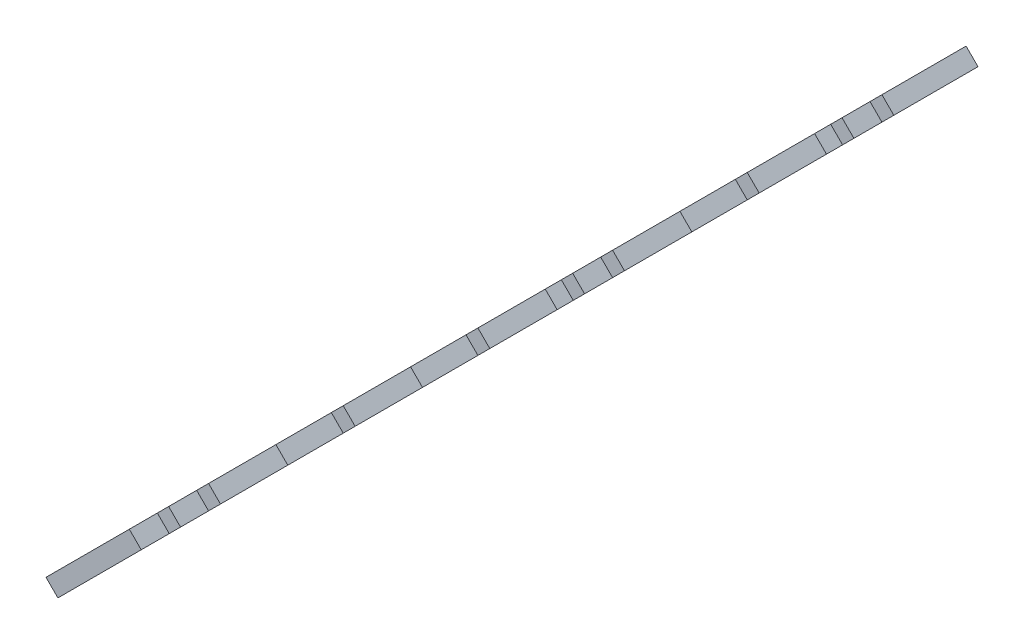
SolidWorks part; units mm, degrees
ref_plane "Front Plane" through (0, 0, 0) normal (0, 0, 1) x (1, 0, 0)
ref_plane "Top Plane" through (0, 0, 0) normal (0, 1, 0) x (1, 0, 0)
ref_plane "Right Plane" through (0, 0, 0) normal (1, 0, 0) x (0, 0, -1)
sketch "Sketch1" plane through (0, 0, 0) normal (0, 0, 1) x (1, 0, 0)
  line L0 (91.6648, 29.3027) -> (52.5461, -9.816) construction
  line L2 (78.5772, 20.7053) -> (74.1015, 16.2295) construction
  line L3 (78.5917, 11.7394) -> (83.0674, 16.2151) construction
  line L4 (39.9621, 9.9289) -> (35.472, 14.4191)
  line L5 (39.9621, 9.9289) -> (71.393, 41.3598)
  line L6 (35.472, 14.4191) -> (66.9029, 45.85)
  line L7 (71.393, 41.3598) -> (66.9029, 45.85)
  line L8 (108.2121, 4.5408) -> (76.7812, -26.8901) construction
  line L9 (76.7812, -26.8901) -> (72.2911, -22.4) construction
  line L10 (103.722, 9.0309) -> (72.2911, -22.4) construction
extrude "Boss-Extrude1" add sketch "Sketch1" along normal up to surface (304.8 mm away)
sketch "Sketch2" plane through (56.3764, 56.3764, 0) normal (0.7071, 0.7071, 0) x (0, 0, -1)
  line L0 (-304.8, -21.2367) -> (0, -21.2367) construction
  line L1 (-279.4, -21.2367) -> (-254, -21.2367)
  line L2 (-279.4, -21.2367) -> (-279.4, -14.8867)
  line L3 (-279.4, -14.8867) -> (-254, -14.8867)
  line L4 (-254, -21.2367) -> (-254, -14.8867)
  line L5 (-304.8, -14.8867) -> (0, -14.8867) construction
  dimension "D1" = 25.4
  dimension "D2" = 25.4
extrude "Boss-Extrude2" add sketch "Sketch2" along normal blind 6.35
pattern_linear "LPattern1" count 6 spacing 50.8 along (0, 0, -1) of "Boss-Extrude2"
sketch "Sketch3" plane through (15.0166, -15.0166, 0) normal (0.7071, -0.7071, 0) x (0, 0, -1)
  circle A0 centre (-273.3375, 57.5033) radius 2.8702
extrude "Cut-Extrude1" cut sketch "Sketch3" against normal up to surface (6.35 mm away) up to face at (66.7302, 45.6773, 155.3308)
sketch "Sketch4" plane through (0, 0, 0) normal (0, 0, -1) x (-1, 0, 0)
  line L0 (-35.472, 14.4191) -> (-39.9621, 9.9289)
  line L1 (-71.393, 50.3401) -> (-35.472, 14.4191) construction
  line L2 (-39.9621, 9.9289) -> (-75.8832, 45.85) construction
  line L3 (-39.9621, 9.9289) -> (-48.9424, 18.9092)
  line L4 (-48.9424, 18.9092) -> (-44.4523, 23.3993)
  line L5 (-44.4523, 23.3993) -> (-35.472, 14.4191)
  dimension "D1" = 12.7
  dimension "D2" = 0
  dimension "D3" = 6.35
extrude "Boss-Extrude3" add sketch "Sketch4" along normal blind 6.35
pattern_linear "LPattern2" count 2 spacing 38.1 along (0.7071, 0.7071, 0) of "Boss-Extrude3"
sketch "Sketch5" plane through (10.5265, -10.5265, 0) normal (-0.7071, 0.7071, 0) x (0.7071, 0.7071, 0)
  line L0 (60.6783, -7.2251) -> (60.6783, -39.5117) construction
  line L1 (47.9783, 6.35) -> (47.9783, 0) construction
  line L2 (73.3783, 6.35) -> (73.3783, 0) construction
  line L3 (73.3783, 0) -> (47.9783, 0) construction
  line B0 (62.8119, 0) -> (58.5447, 0)
  line B1 (58.5447, -11.938) -> (56.2333, -11.938)
  line B2 (56.2333, -11.938) -> (56.2333, -8.763)
  line B3 (56.2333, -8.763) -> (58.5447, -8.763)
  line B4 (58.5447, -8.763) -> (58.5447, 0)
  line B5 (58.5447, -11.938) -> (58.5447, -15.24)
  line B6 (58.5447, -15.24) -> (62.8119, -15.24)
  line B7 (62.8119, -11.938) -> (62.8119, -15.24)
  line B8 (62.8119, -8.763) -> (62.8119, 0)
  line B9 (65.1233, -8.763) -> (62.8119, -8.763)
  line B10 (65.1233, -11.938) -> (65.1233, -8.763)
  line B11 (62.8119, -11.938) -> (65.1233, -11.938)
sketch_block_instance "TSlot-1"
sketch_block "TSlot" parameters "D1"=3.302, "D2"=3.175
extrude "Cut-Extrude2" cut sketch "Sketch5" against normal through all
sketch "Sketch6" plane through (10.5265, -10.5265, 0) normal (-0.7071, 0.7071, 0) x (0.7071, 0.7071, 0)
  line L0 (79.7283, -292.1) -> (47.6349, -292.1) construction
  line L1 (79.7283, -304.8) -> (79.7283, -279.4) construction
  line L2 (79.7283, -139.7) -> (53.7612, -139.7) construction
  line L3 (79.7283, -152.4) -> (79.7283, -127) construction
  line L4 (79.7283, -38.1) -> (53.7612, -38.1) construction
  line L5 (79.7283, -50.8) -> (79.7283, -25.4) construction
  line L6 (86.0783, -25.4) -> (79.7283, -25.4) construction
  line L7 (86.0783, -50.8) -> (79.7283, -50.8) construction
  line L8 (86.0783, -127) -> (79.7283, -127) construction
  line L9 (86.0783, -152.4) -> (79.7283, -152.4) construction
  line L10 (86.0783, -279.4) -> (79.7283, -279.4) construction
  line L11 (35.2783, -304.8) -> (79.7283, -304.8) construction
  line B0 (79.7283, -294.2336) -> (79.7283, -289.9664)
  line B1 (67.7903, -289.9664) -> (67.7903, -287.655)
  line B2 (67.7903, -287.655) -> (70.9653, -287.655)
  line B3 (70.9653, -287.655) -> (70.9653, -289.9664)
  line B4 (70.9653, -289.9664) -> (79.7283, -289.9664)
  line B5 (67.7903, -289.9664) -> (64.4883, -289.9664)
  line B6 (64.4883, -289.9664) -> (64.4883, -294.2336)
  line B7 (67.7903, -294.2336) -> (64.4883, -294.2336)
  line B8 (70.9653, -294.2336) -> (79.7283, -294.2336)
  line B9 (70.9653, -296.545) -> (70.9653, -294.2336)
  line B10 (67.7903, -296.545) -> (70.9653, -296.545)
  line B11 (67.7903, -294.2336) -> (67.7903, -296.545)
  line B12 (79.7283, -141.8336) -> (79.7283, -137.5664)
  line B13 (67.7903, -137.5664) -> (67.7903, -135.255)
  line B14 (67.7903, -135.255) -> (70.9653, -135.255)
  line B15 (70.9653, -135.255) -> (70.9653, -137.5664)
  line B16 (70.9653, -137.5664) -> (79.7283, -137.5664)
  line B17 (67.7903, -137.5664) -> (64.4883, -137.5664)
  line B18 (64.4883, -137.5664) -> (64.4883, -141.8336)
  line B19 (67.7903, -141.8336) -> (64.4883, -141.8336)
  line B20 (70.9653, -141.8336) -> (79.7283, -141.8336)
  line B21 (70.9653, -144.145) -> (70.9653, -141.8336)
  line B22 (67.7903, -144.145) -> (70.9653, -144.145)
  line B23 (67.7903, -141.8336) -> (67.7903, -144.145)
  line B24 (79.7283, -40.2336) -> (79.7283, -35.9664)
  line B25 (67.7903, -35.9664) -> (67.7903, -33.655)
  line B26 (67.7903, -33.655) -> (70.9653, -33.655)
  line B27 (70.9653, -33.655) -> (70.9653, -35.9664)
  line B28 (70.9653, -35.9664) -> (79.7283, -35.9664)
  line B29 (67.7903, -35.9664) -> (64.4883, -35.9664)
  line B30 (64.4883, -35.9664) -> (64.4883, -40.2336)
  line B31 (67.7903, -40.2336) -> (64.4883, -40.2336)
  line B32 (70.9653, -40.2336) -> (79.7283, -40.2336)
  line B33 (70.9653, -42.545) -> (70.9653, -40.2336)
  line B34 (67.7903, -42.545) -> (70.9653, -42.545)
  line B35 (67.7903, -40.2336) -> (67.7903, -42.545)
sketch_block_instance "TSlot-2"
sketch_block_instance "TSlot-3"
sketch_block_instance "TSlot-4"
extrude "Cut-Extrude3" cut sketch "Sketch6" against normal through all
sketch "Sketch7" plane through (15.0166, -15.0166, 0) normal (0.7071, -0.7071, 0) x (-0.7071, -0.7071, 0)
  line L0 (-86.0783, -213.6951) -> (-79.7283, -217.9623) construction
  line L1 (-79.7283, -213.6951) -> (-86.0783, -217.9623) construction
  line L2 (-86.0783, -228.6) -> (-86.0783, -203.2) construction
  line L3 (-86.0783, -217.9623) -> (-79.7283, -217.9623) construction
  line L4 (-86.0783, -65.5623) -> (-79.7283, -61.2951) construction
  line L5 (-86.0783, -65.5623) -> (-79.7283, -65.5623) construction
  line L6 (-86.0783, -76.2) -> (-86.0783, -50.8) construction
  line L7 (-79.7283, -65.5623) -> (-86.0783, -61.2951) construction
  line L8 (-79.7283, -61.2951) -> (-86.0783, -61.2951) construction
  circle A0 centre (-82.9033, -215.8287) radius 2.0955
  circle A1 centre (-82.9033, -63.4287) radius 2.0955
  dimension "D1" = 4.191
extrude "Cut-Extrude4" cut sketch "Sketch7" against normal through all
